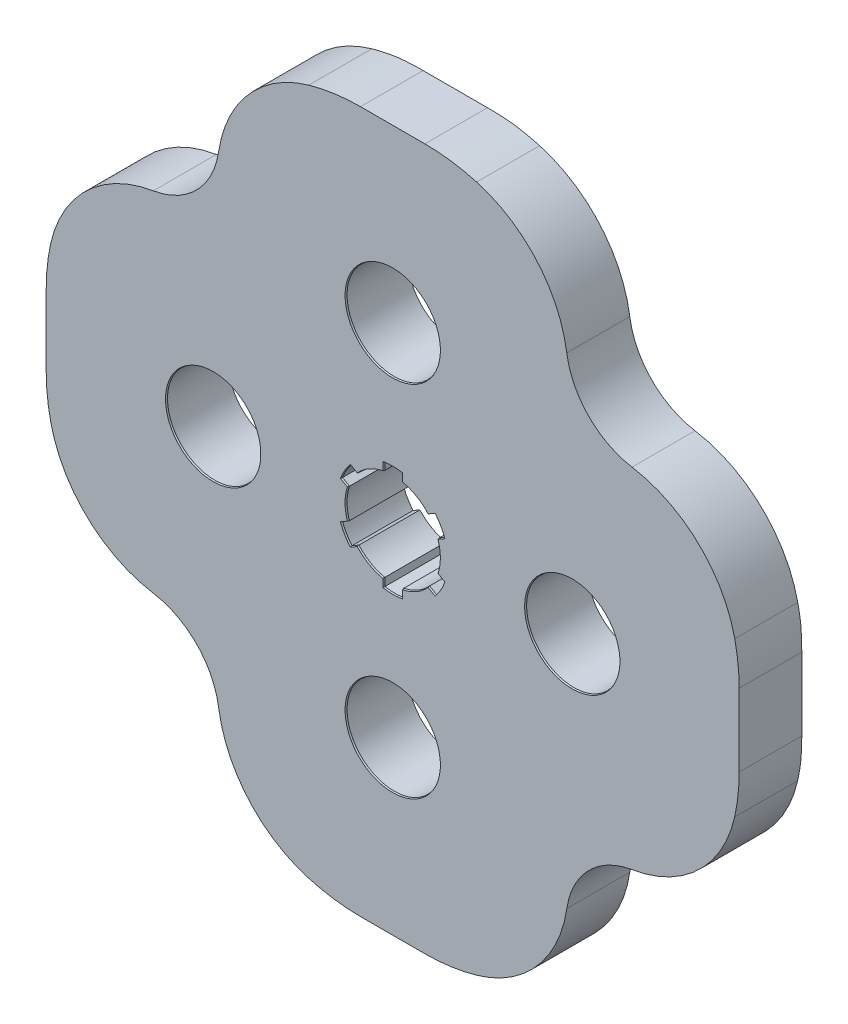
SolidWorks part; units mm, degrees
ref_plane "Front Plane" through (0, 0, 0) normal (0, 0, 1) x (1, 0, 0)
ref_plane "Top Plane" through (0, 0, 0) normal (0, 1, 0) x (1, 0, 0)
ref_plane "Right Plane" through (0, 0, 0) normal (1, 0, 0) x (0, 0, -1)
sketch "Sketch1" plane through (0, 0, 0) normal (0, 0, 1) x (1, 0, 0)
  line L0 (-110, 36.4087) -> (-35.07, 111.3387)
  line L1 (-35.07, 111.3387) -> (35.07, 111.3387)
  line L2 (-110, 36.4087) -> (-110, -36.3387)
  line L3 (-35, -111.3387) -> (35, -111.3387)
  line L4 (110, 36.4087) -> (110, -36.3387)
  line L5 (-110, 111.3387) -> (110, -111.3387) construction
  line L6 (-110, -111.3387) -> (110, 111.3387) construction
  line L7 (35.07, 111.3387) -> (110, 36.4087)
  line L8 (35, -111.3387) -> (110, -36.3387)
  line L9 (-110, -36.3387) -> (-35, -111.3387)
  point P0 (0, 0)
  dimension "D1" = 220
  dimension "D2" = 222.6775
extrude "Boss-Extrude1" add sketch "Sketch1" along normal blind 20
sketch "Sketch2" plane through (0, 0, 20) normal (0, 0, 1) x (1, 0, 0)
  line L0 (3, 17.2409) -> (3, 14.6969)
  line L1 (-3, 17.2409) -> (-3, 14.6969)
  line L2 (0, -55) -> (0, 55) construction
  line L3 (16.4311, 6.0224) -> (14.2279, 4.7504)
  line L4 (13.4311, 11.2185) -> (11.2279, 9.9465)
  line L5 (13.4311, -11.2185) -> (11.2279, -9.9465)
  line L6 (16.4311, -6.0224) -> (14.2279, -4.7504)
  line L7 (-3, -17.2409) -> (-3, -14.6969)
  line L8 (3, -17.2409) -> (3, -14.6969)
  line L9 (-16.4311, -6.0224) -> (-14.2279, -4.7504)
  line L10 (-13.4311, -11.2185) -> (-11.2279, -9.9465)
  line L11 (-13.4311, 11.2185) -> (-11.2279, 9.9465)
  line L12 (-16.4311, 6.0224) -> (-14.2279, 4.7504)
  line L13 (0, 0) -> (3, 14.6969) construction
  circle A0 centre (0, 0) radius 15
  circle A1 centre (0, 0) radius 17.5
  dimension "D1" = 30
  dimension "D2" = 35
  dimension "D3" = 3
  dimension "D4" = 3
  dimension "D6" = 15
  dimension "D5" = 6
extrude "Cut-Extrude1" cut sketch "Sketch2" against normal blind 35
chamfer "Chamfer1" distance 0.5 angle 15 56 edges at (0, 17.5, 20) (-3, 15.9689, 20) (-7.5, 12.9904, 20) (-12.3295, 10.5825, 20) (-15.1554, 8.75, 20) (-15.3295, 5.3864, 20) (-15, 0, 20) (-15.3295, -5.3864, 20) (-15.1554, -8.75, 20) (-12.3295, -10.5825, 20) (-7.5, -12.9904, 20) (-3, -15.9689, 20) (0, -17.5, 20) (3, -15.9689, 20) (7.5, -12.9904, 20) (12.3295, -10.5825, 20) (15.1554, -8.75, 20) (15.3295, -5.3864, 20) (15, 0, 20) (15.3295, 5.3864, 20) (15.1554, 8.75, 20) (12.3295, 10.5825, 20) (7.5, 12.9904, 20) (3, 15.9689, 20) (12.3295, 10.5825, 0) (15.1554, 8.75, 0) (15.3295, 5.3864, 0) (15, 0, 0) (15.3295, -5.3864, 0) (15.1554, -8.75, 0) (12.3295, -10.5825, 0) (7.5, -12.9904, 0) (3, -15.9689, 0) (0, -17.5, 0) (-3, -15.9689, 0) (-7.5, -12.9904, 0) (-12.3295, -10.5825, 0) (-15.1554, -8.75, 0) (-15.3295, -5.3864, 0) (-15, 0, 0) (-15.3295, 5.3864, 0) (-15.1554, 8.75, 0) (-12.3295, 10.5825, 0) (-7.5, 12.9904, 0) (-3, 15.9689, 0) (0, 17.5, 0) (3, 15.9689, 0) (7.5, 12.9904, 0) (-72.535, 73.8737, 0) (-110, 0.035, 0) (-72.5, -73.8387, 0) (0, -111.3387, 0) (72.5, -73.8387, 0) (110, 0.035, 0) (72.535, 73.8737, 0) (0, 111.3387, 0)
sketch "Sketch3" plane through (0, 0, 0) normal (0, 0, -1) x (-1, 0, 0)
  circle A0 centre (0, 0) radius 57 construction
  circle A1 centre (0, 57) radius 15
  circle A2 centre (-57, 0) radius 15
  circle A3 centre (57, 0) radius 15
  circle A4 centre (0, -57) radius 15
  dimension "D1" = 114
  dimension "D2" = 30
  dimension "D3" = 30
  dimension "D4" = 30
  dimension "D5" = 30
extrude "Cut-Extrude2" cut sketch "Sketch3" against normal blind 35
fillet "Fillet1" radius 60 8 edges at (-110, 36.4087, 10.067) (-110, -36.3387, 10.067) (-35, -111.3387, 10.067) (35, -111.3387, 10.067) (110, -36.3387, 10.067) (110, 36.4087, 10.067) (35.07, 111.3387, 10.067) (-35.07, 111.3387, 10.067)
chamfer "Chamfer2" distance 0.5 angle 15 8 edges at (-15, 57, 20) (-15, 57, 0) (-15, -57, 20) (42, 0, 20) (-72, 0, 20) (42, 0, 0) (-15, -57, 0) (-72, 0, 0)
sketch "Sketch6" plane through (0, 0, 20) normal (0, 0, 1) x (1, 0, 0)
  circle A0 centre (80, 80.01) radius 25
  dimension "D1" = 50
  dimension "D3" = 80
  dimension "D2" = 80.01
extrude "Cut-Extrude3" cut sketch "Sketch6" against normal blind 35
pattern_circular "CirPattern1" count 4 over 360 about axis through (0, 0, 0) along (0, 0, 1) of "Cut-Extrude3"
fillet "Fillet2" radius 40 8 edges at (89.477, -56.8618, 10.067) (56.8718, -89.467, 10.067) (-56.8618, -89.477, 10.067) (-89.467, -56.8718, 10.067) (-89.5266, 56.8822, 10.067) (-56.8922, 89.5166, 10.067) (56.8822, 89.5266, 10.067) (89.5166, 56.8922, 10.067)
